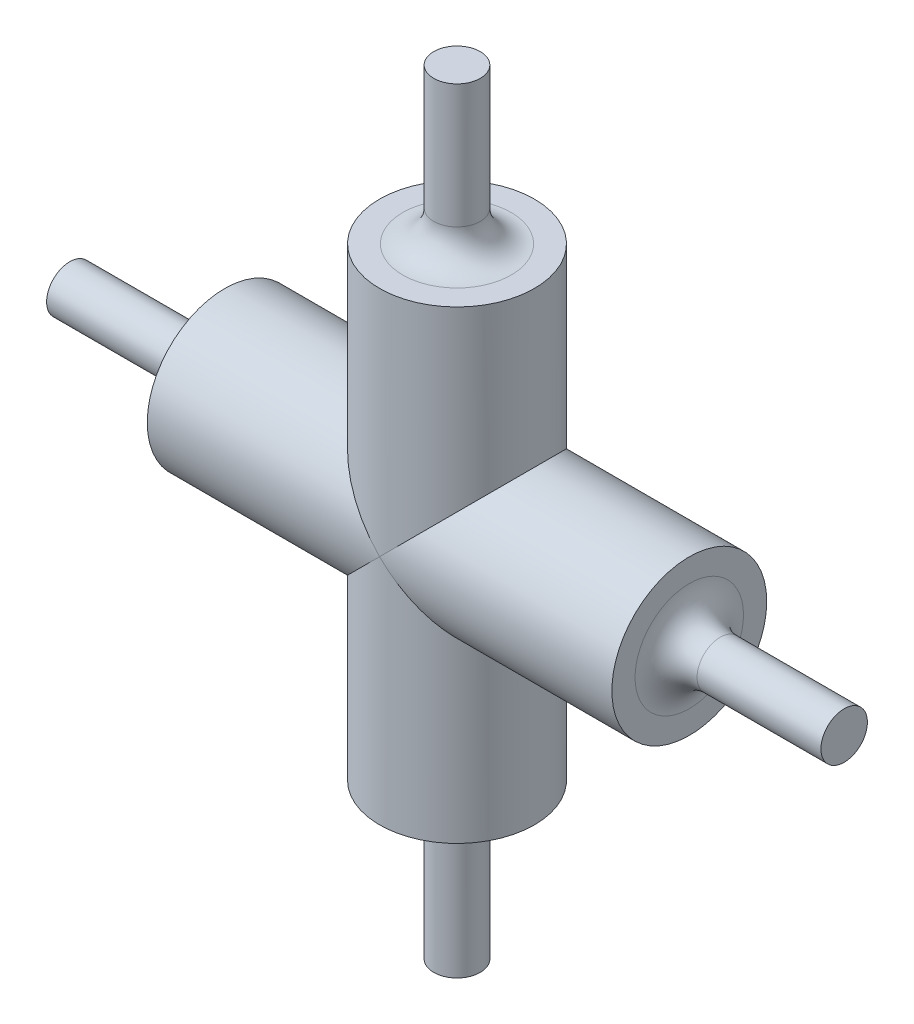
SolidWorks part; units mm, degrees
ref_plane "前视基准面" through (0, 0, 0) normal (0, 0, 1) x (1, 0, 0)
ref_plane "上视基准面" through (0, 0, 0) normal (0, 1, 0) x (1, 0, 0)
ref_plane "右视基准面" through (0, 0, 0) normal (1, 0, 0) x (0, 0, -1)
other "Configuration Table"
sketch "草图1" plane through (0, 0, 0) normal (0, 1, 0) x (1, 0, 0)
  circle A0 centre (0, 0) radius 10
  dimension "D1" = 20
extrude "凸台-拉伸1" add sketch "草图1" along normal mid plane 100
sketch "草图2" plane through (0, 0, 0) normal (1, 0, 0) x (0, 0, -1)
  circle A0 centre (0, 0) radius 10
  dimension "D1" = 20
extrude "凸台-拉伸2" add sketch "草图2" along normal mid plane 100
sketch "草图3" plane through (-50, 0, 0) normal (-1, 0, 0) x (0, 0, 1)
  circle A0 centre (0, 0) radius 3
  dimension "D1" = 6
extrude "切除-拉伸1" cut sketch "草图3" against normal blind 20 flip side to cut
fillet "圆角2" radius 4 1 edges at (-30, 0, 3)
ref_axis "基准轴2" through (0, 0, 11) along (0, 0, -1)
pattern_circular "阵列(圆周)1" count 4 every 90 about axis through (0, 0, 11) along (0, 0, -1) of "切除-拉伸1", "圆角2"
